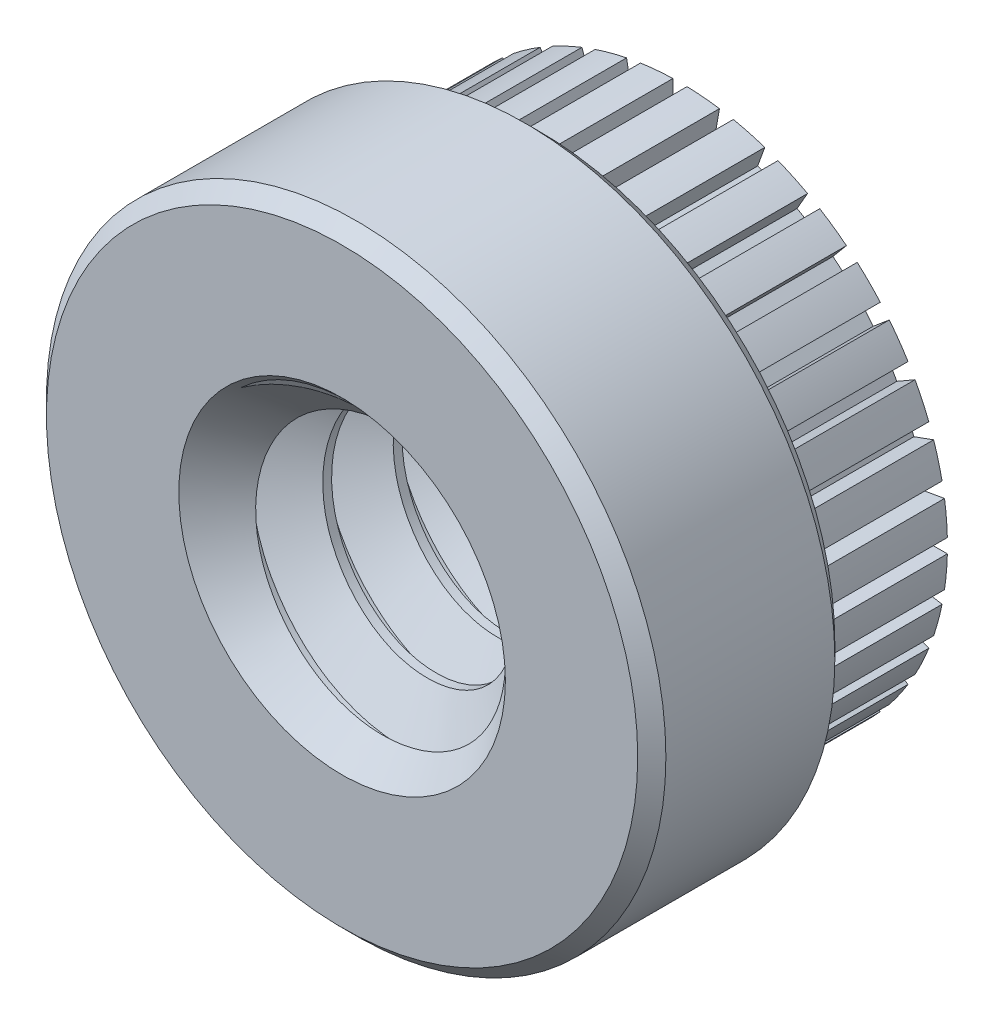
SolidWorks part; units mm, degrees
ref_plane "Front Plane" through (0, 0, 0) normal (0, 0, 1) x (1, 0, 0)
ref_plane "Top Plane" through (0, 0, 0) normal (0, 1, 0) x (1, 0, 0)
ref_plane "Right Plane" through (0, 0, 0) normal (1, 0, 0) x (0, 0, -1)
sketch "Sketch1" plane through (0, 0, 0) normal (0, 0, 1) x (1, 0, 0)
  circle A0 centre (0, 0) radius 2.794
  dimension "A" = 5.588
extrude "Extrude1" add sketch "Sketch1" against normal blind 1.778
sketch "Sketch2" plane through (0, 0, -1.778) normal (0, 0, -1) x (-1, 0, 0)
  circle A0 centre (0, 0) radius 2.413
  dimension "C" = 4.826
extrude "Extrude2" add sketch "Sketch2" along normal blind 1.524
sketch "Sketch3" plane through (0, 0, -3.302) normal (0, 0, -1) x (-1, 0, 0)
  line L0 (0, 2.2225) -> (0, 2.794)
  circle A1 centre (0, 0) radius 2.794 construction
  circle A2 centre (0, 0) radius 2.2225
  circle A3 centre (0, 0) radius 2.2225 construction
  dimension "D1" = 0.1905
extrude "Cut-Extrude-Thin1" cut sketch "Sketch3" against normal up to surface (1.524 mm away) thin up to face at (2.794, 0, -1.778) thin type mid plane wall 0.127
pattern_circular "CirPattern1" count 36 over 360 about axis through (0, 0, -1.778) along (0, 0, 1) of "Cut-Extrude-Thin1"
sketch "Sketch5" plane through (0, 0, -3.302) normal (0, 0, -1) x (-1, 0, 0)
  circle A2 centre (0, 0) radius 1.9685
  circle A3 centre (0, 0) radius 1.9685
  dimension "D1" = 0.254
extrude "Cut-Extrude1" cut sketch "Sketch5" against normal blind 0.254 flip side to cut
chamfer "Chamfer1" distance 0.127 angle 45 1 edges at (-1.9685, 0, -3.302)
sketch "Sketch6" plane through (0, 0, -1.778) normal (0, 0, -1) x (-1, 0, 0)
  circle A0 centre (0, 0) radius 1.9685 construction
  circle A1 centre (0, 0) radius 1.9685
  circle A2 centre (0, 0) radius 2.794 construction
  circle A3 centre (0, 0) radius 2.794
extrude "Cut-Extrude2" cut sketch "Sketch6" along normal blind 0.127
chamfer "Chamfer2" distance 0.127 angle 45 2 edges at (2.794, 0, 0) (2.794, 0, -1.778)
sketch "Sketch7" plane through (0, 0, 0) normal (0, 0, 1) x (1, 0, 0)
  circle A0 centre (0, 0) radius 1.4224
  dimension "Thread Od" = 2.8448
extrude "Cut-Extrude3" cut sketch "Sketch7" against normal through all
sketch "Sketch8" plane through (0, 0, -3.302) normal (0, 0, -1) x (-1, 0, 0)
  circle A0 centre (0, 0) radius 1.4224 construction
  circle A1 centre (0, 0) radius 1.4224
curve "Helix/Spiral1" pitch 0.635 height 4.953 radius 1.4224 centre (0, 0, -3.302) axis (0, 0, 1) start towards (0, 1, 0) parameters "pitch"=0.635
sketch "Sketch9" plane through (0, 0, 0) normal (1, 0, 0) x (0, 0, -1)
  line L0 (3.8576, 1.4224) -> (3.6195, 1.01)
  line L1 (3.6195, 1.01) -> (3.5401, 1.01)
  line L2 (3.5401, 1.01) -> (3.302, 1.4224)
  line L3 (3.8576, 1.4224) -> (3.302, 1.4224)
  line L4 (3.5798, 1.4224) -> (3.5798, 1.01) construction
  line L5 (3.7386, 1.2162) -> (3.4211, 1.2162) construction
  line L6 (3.302, -1.4224) -> (3.302, 1.4224) construction
  dimension "D1" = 60
  dimension "D2" = 0.0794
  dimension "D3" = 0.3175
sweep "Sweep1" add profiles "Sketch9" path "Helix/Spiral1"
sketch "Sketch10" plane through (0, 0, 0) normal (0, 0, 1) x (1, 0, 0)
  circle A1 centre (0, 0) radius 2.667
  circle A2 centre (0, 0) radius 2.667
  dimension "D1" = 0
extrude "Cut-Extrude4" cut sketch "Sketch10" along normal through all
sketch "Sketch11" plane through (0, 0, -3.302) normal (0, 0, -1) x (-1, 0, 0)
  circle A0 centre (0, 0) radius 1.8415 construction
  circle A1 centre (0, 0) radius 1.8415
extrude "Cut-Extrude5" cut sketch "Sketch11" along normal through all
sketch "Sketch13" plane through (0, 0, 0) normal (0, 0, 1) x (1, 0, 0)
  circle A2 centre (0, 0) radius 1.4732
  circle A3 centre (0, 0) radius 1.4732
  dimension "D1" = 0.0508
extrude "Cut-Extrude6" cut sketch "Sketch13" against normal through all draft 45
sketch "Sketch14" plane through (0, 0, -3.302) normal (0, 0, -1) x (-1, 0, 0)
  circle A2 centre (0, 0) radius 1.4732
  circle A3 centre (0, 0) radius 1.4732
  dimension "D1" = 0.0508
extrude "Cut-Extrude7" cut sketch "Sketch14" against normal through all draft 45
equation "\"D3@Helix/Spiral1\" = \"B@Extrude1\"+.125"
equation "\"D2@Sketch9\" = \"pitch@Helix/Spiral1\"*.125"
equation "\"D3@Sketch9\" = \"pitch@Helix/Spiral1\"*.50"
